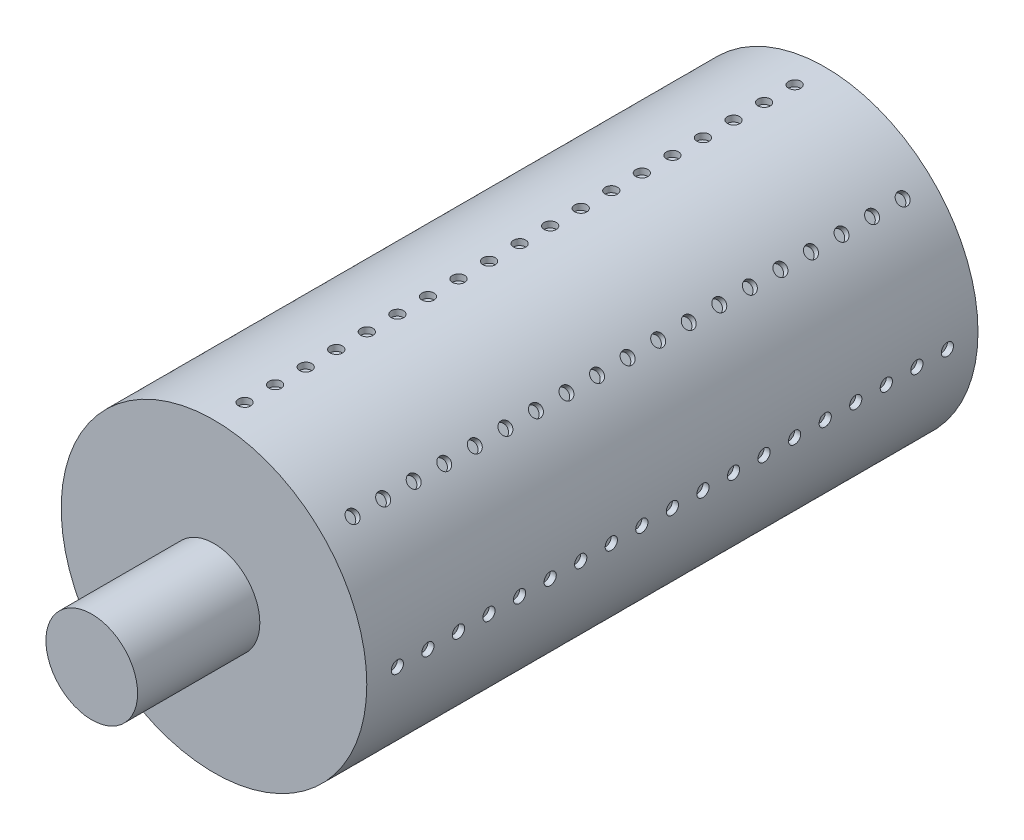
SolidWorks part; units mm, degrees
material "XB450"
ref_plane "前视基准面" through (0, 0, 0) normal (0, 0, 1) x (1, 0, 0)
ref_plane "上视基准面" through (0, 0, 0) normal (0, 1, 0) x (1, 0, 0)
ref_plane "右视基准面" through (0, 0, 0) normal (1, 0, 0) x (0, 0, -1)
sketch "草图1" plane through (0, 0, 0) normal (0, 0, 1) x (1, 0, 0)
  circle A0 centre (0, 0) radius 25
  dimension "D1" = 50
sketch "草图2" plane through (0, 0, 0) normal (0, 1, 0) x (1, 0, 0)
  line L0 (0, 0) -> (0, 100)
  line L1 (-25, 0) -> (25, 0) construction
  dimension "D1" = 100
sweep "扫描1" add profiles "草图1" path "草图2"
ref_plane "基准面4" through (0, 30, 0) normal (0, 1, 0) x (1, 0, 0)
sketch "草图3" plane through (0, 30, 0) normal (0, 1, 0) x (1, 0, 0)
  line L0 (0, 111.1487) -> (0, -13.778) construction
  line L1 (52.3853, 50) -> (-55.1536, 50) construction
  line L2 (25, 100) -> (-25, 100) construction
  circle A0 centre (0, 50) radius 1
  circle A1 centre (0, 55) radius 1
  circle A2 centre (0, 60) radius 1
  circle A3 centre (0, 65) radius 1
  circle A4 centre (0, 70) radius 1
  circle A5 centre (0, 75) radius 1
  circle A6 centre (0, 80) radius 1
  circle A7 centre (0, 85) radius 1
  circle A8 centre (0, 90) radius 1
  circle A9 centre (0, 95) radius 1
  circle A10 centre (0, 5) radius 1
  circle A11 centre (0, 10) radius 1
  circle A12 centre (0, 15) radius 1
  circle A13 centre (0, 20) radius 1
  circle A14 centre (0, 25) radius 1
  circle A15 centre (0, 30) radius 1
  circle A16 centre (0, 35) radius 1
  circle A17 centre (0, 40) radius 1
  circle A18 centre (0, 45) radius 1
  dimension "D2" = 2
  dimension "D3" = 2
  dimension "D12" = 45
  dimension "D1" = 50
  dimension "D4" = 5
  dimension "D5" = 10
  dimension "D6" = 15
  dimension "D7" = 20
  dimension "D8" = 25
  dimension "D9" = 30
  dimension "D10" = 35
  dimension "D11" = 40
extrude "切除-拉伸1" cut sketch "草图3" against normal blind 6
pattern_circular "阵列(圆周)1" count 8 over 360 about axis through (0, 0, -100) along (0, 0, 1) of "切除-拉伸1"
sketch "草图4" plane through (0, 0, -100) normal (0, 0, -1) x (-1, 0, 0)
  line L1 (-10, 2.5) -> (10, 2.5)
  line L2 (-10, 2.5) -> (-10, -2.5)
  line L3 (-10, -2.5) -> (10, -2.5)
  line L4 (10, 2.5) -> (10, -2.5)
  line L5 (-10, 2.5) -> (10, -2.5) construction
  line L6 (-10, -2.5) -> (10, 2.5) construction
  point P0 (0, 0)
  dimension "D1" = 5
  dimension "D2" = 20
extrude "切除-拉伸2" cut sketch "草图4" against normal blind 5
sketch "草图6" plane through (0, 0, 0) normal (0, 0, 1) x (1, 0, 0)
  circle A0 centre (0, 0) radius 7.5
  dimension "D1" = 15
extrude "凸台-拉伸1" add sketch "草图6" along normal blind 20
